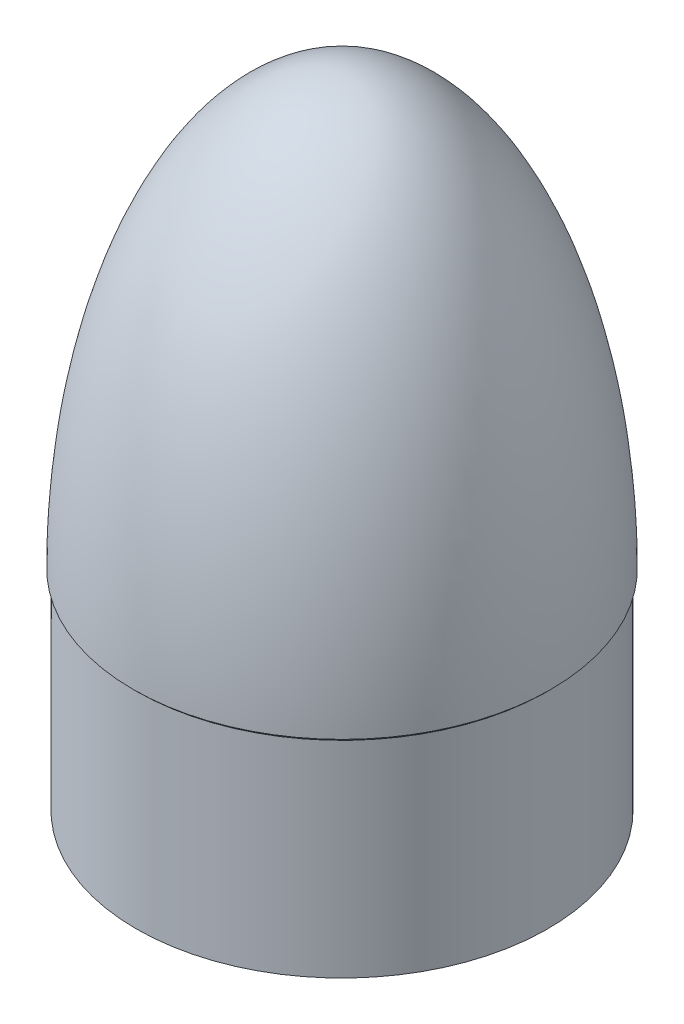
SolidWorks part; units mm, degrees
ref_plane "Front Plane" through (0, 0, 0) normal (0, 0, 1) x (1, 0, 0)
ref_plane "Top Plane" through (0, 0, 0) normal (0, 1, 0) x (1, 0, 0)
ref_plane "Right Plane" through (0, 0, 0) normal (1, 0, 0) x (0, 0, -1)
sketch "Sketch1" plane through (0, 0, 0) normal (0, 0, 1) x (1, 0, 0)
  line L3 (0, 0) -> (0, 202.3003) construction
  line L5 (0, 165.1) -> (0, 162.1028)
  line L10 (76.3778, 0) -> (76.3778, -80.518)
  line L12 (76.3778, -80.518) -> (79.375, -80.518)
  line L13 (79.375, -80.518) -> (79.375, -1.143)
  line L14 (80.518, 0) -> (79.375, -1.143)
  line L15 (79.375, -1.143) -> (80.518, -1.143) construction
  ellipse E0 centre (0, 0) end of major axis (0, 162.1028) minor radius 76.3778 (76.3778, 0) -> (0, 162.1028) ccw
  ellipse E1 centre (0, 0) end of major axis (0, -165.1) minor radius 80.518 (80.518, 0) -> (0, 165.1) ccw
  dimension "D1" = 158.75
  dimension "D2" = 79.375
  dimension "D3" = 165.1
  dimension "D4" = 161.036
  dimension "D5" = 2.9972
  dimension "D6" = 2.9972
  dimension "D7" = 45
revolve "Revolve1" add sketch "Sketch1" angle 360 about L5
